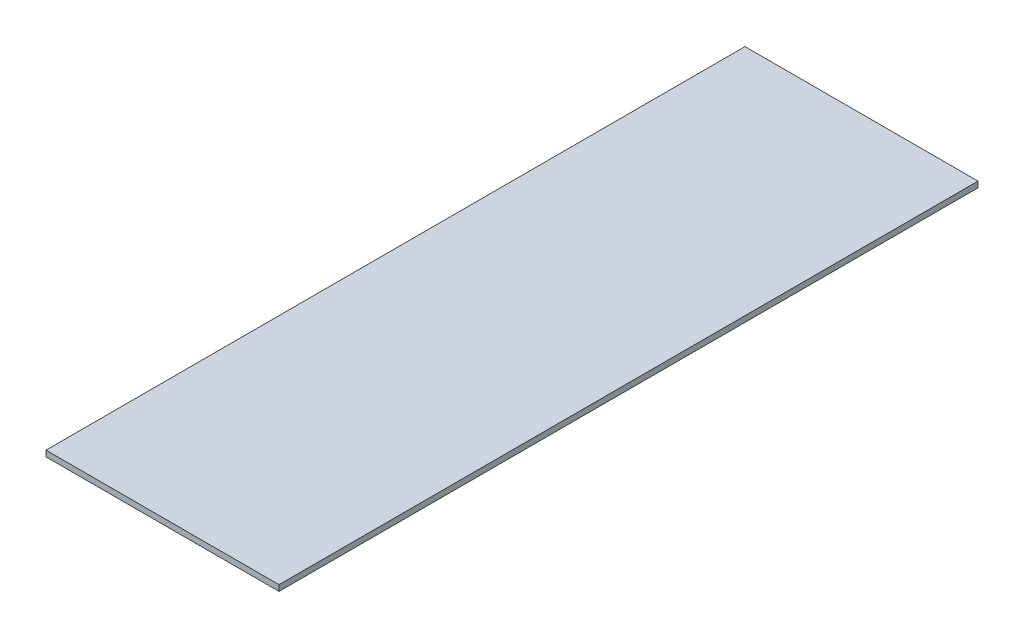
SolidWorks part; units mm, degrees
ref_plane "Front Plane" through (0, 0, 0) normal (0, 0, 1) x (1, 0, 0)
ref_plane "Top Plane" through (0, 0, 0) normal (0, 1, 0) x (1, 0, 0)
ref_plane "Right Plane" through (0, 0, 0) normal (1, 0, 0) x (0, 0, -1)
sketch "Sketch1" plane through (0, 0, 0) normal (0, 1, 0) x (1, 0, 0)
  line L1 (-127, 381) -> (127, 381)
  line L2 (-127, 381) -> (-127, -381)
  line L3 (-127, -381) -> (127, -381)
  line L4 (127, 381) -> (127, -381)
  line L5 (-127, 381) -> (127, -381) construction
  line L6 (-127, -381) -> (127, 381) construction
  point P0 (0, 0)
  dimension "D1" = 254
  dimension "D2" = 762
extrude "Boss-Extrude1" add sketch "Sketch1" along normal blind 3.175 and the other way blind 3.175
